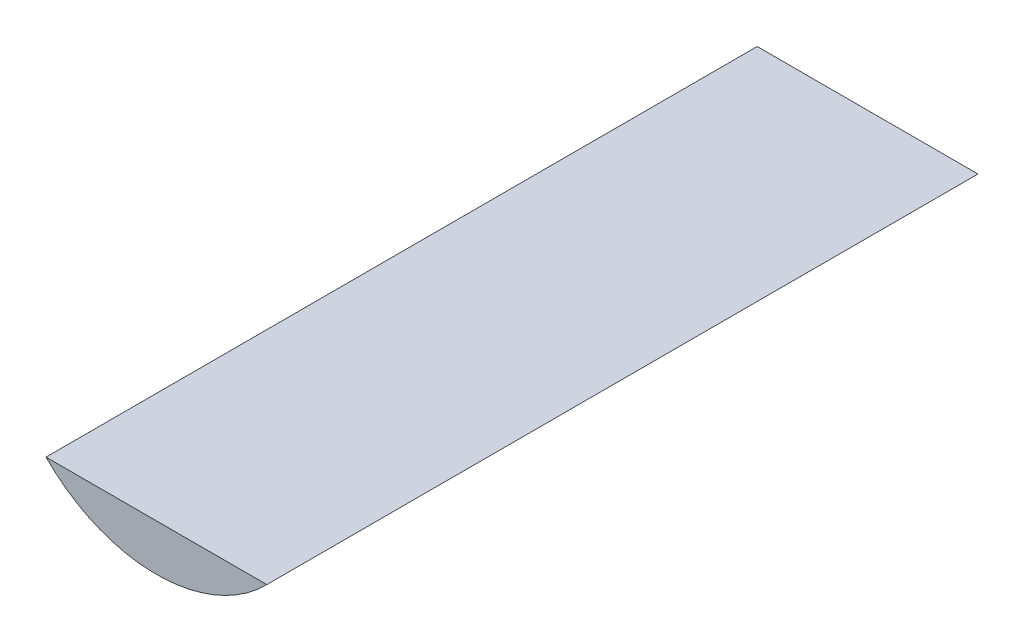
SolidWorks part; units mm, degrees
ref_plane "Front" through (0, 0, 0) normal (0, 0, 1) x (1, 0, 0)
ref_plane "Top" through (0, 0, 0) normal (0, 1, 0) x (1, 0, 0)
ref_plane "Right" through (0, 0, 0) normal (1, 0, 0) x (0, 0, -1)
sketch "Sketch1" plane through (0, 0, 0) normal (0, 0, 1) x (1, 0, 0)
  line L0 (-35.7071, -35) -> (35.7071, -35)
  line L1 (0, -50) -> (0, -35) construction
  arc A0 (-35.7071, -35) -> (35.7071, -35) centre (0, 0) ccw
  dimension "D1" = 100
  dimension "D2" = 15
extrude "Boss-Extrude1" add sketch "Sketch1" along normal blind 230
